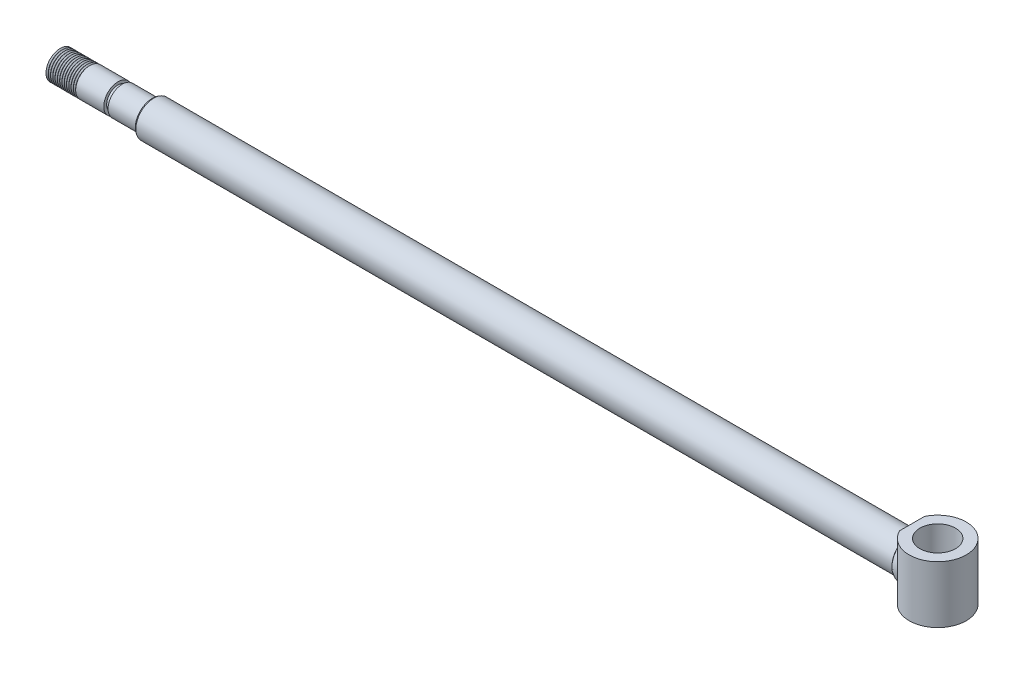
SolidWorks part; units mm, degrees
ref_plane "Front Plane" through (0, 0, 0) normal (0, 0, 1) x (1, 0, 0)
ref_plane "Top Plane" through (0, 0, 0) normal (0, 1, 0) x (1, 0, 0)
ref_plane "Right Plane" through (0, 0, 0) normal (1, 0, 0) x (0, 0, -1)
sketch "Sketch1" plane through (0, 0, 0) normal (0, 0, 1) x (1, 0, 0)
  line L0 (0, 0) -> (635, 0) construction
  line L1 (0, 0) -> (0, 10)
  line L2 (0, 0) -> (597, 0)
  line L3 (64.5, 10) -> (64.5, 12.5)
  line L4 (64.5, 12.5) -> (597, 12.5)
  line L5 (597, 12.5) -> (597, 0)
  line L6 (19.5, 10) -> (19.5, 0) construction
  line L7 (64.5, 10) -> (64.5, 0) construction
  line L8 (19.5, 5) -> (64.5, 5) construction
  line L9 (40.5, 10) -> (40.5, 8)
  line L10 (40.5, 8) -> (43.5, 8)
  line L11 (43.5, 8) -> (43.5, 10)
  line L12 (42, 5) -> (42, 10) construction
  line L13 (43.5, 10) -> (64.5, 10)
  line L14 (0, 10) -> (0.8, 9.2)
  line L15 (0.8, 9.2) -> (1.6, 10)
  line L16 (0.8, 9.2) -> (0.8, 10) construction
  line L17 (1.6, 10) -> (2.4, 9.2)
  line L18 (2.4, 9.2) -> (3.2, 10)
  line L19 (3.2, 10) -> (4, 9.2)
  line L20 (4, 9.2) -> (4.8, 10)
  line L21 (4.8, 10) -> (5.6, 9.2)
  line L22 (5.6, 9.2) -> (6.4, 10)
  line L23 (6.4, 10) -> (7.2, 9.2)
  line L24 (7.2, 9.2) -> (8, 10)
  line L25 (8, 10) -> (8.8, 9.2)
  line L26 (8.8, 9.2) -> (9.6, 10)
  line L27 (9.6, 10) -> (10.4, 9.2)
  line L28 (10.4, 9.2) -> (11.2, 10)
  line L29 (11.2, 10) -> (12, 9.2)
  line L30 (12, 9.2) -> (12.8, 10)
  line L31 (12.8, 10) -> (13.6, 9.2)
  line L32 (13.6, 9.2) -> (14.4, 10)
  line L33 (14.4, 10) -> (15.2, 9.2)
  line L34 (15.2, 9.2) -> (16, 10)
  line L35 (16, 10) -> (16.8, 9.2)
  line L36 (16.8, 9.2) -> (17.6, 10)
  line L37 (17.6, 10) -> (18.4, 9.2)
  line L38 (18.4, 9.2) -> (19.2, 10)
  line L39 (19.2, 10) -> (20, 9.2)
  line L40 (20, 9.2) -> (20.8, 10)
  line L41 (20.8, 10) -> (40.5, 10)
  dimension "D1" = 635
  dimension "D2" = 25
  dimension "D3" = 38
  dimension "D4" = 64.5
  dimension "D6" = 45
  dimension "D7" = 1.5
  dimension "D8" = 1.5
  dimension "D11" = 1.6
  dimension "D12" = 13
revolve "Revolve1" add sketch "Sketch1" angle 360 about L2
chamfer "Chamfer1" distance 1 angle 30 1 edges at (64.5, 0, 12.5) first distance on face at (64.5, 0, 12.5)
sketch "Sketch2" plane through (0, 0, 0) normal (0, 1, 0) x (1, 0, 0)
  line L0 (597, -12.5) -> (597, 12.5) construction
  line L1 (597, -12.5) -> (597, 12.5) construction
  line L2 (597, 0) -> (635, 0) construction
  line L3 (635, 0) -> (597, 0) construction
  line L4 (597, 0) -> (597, -8.7178)
  line L5 (597, 0) -> (597, 8.7178)
  arc A0 (597, -8.7178) -> (597, 8.7178) centre (615, 0) ccw
  circle A1 centre (615, 0) radius 12.5
  dimension "D2" = 40
  dimension "D3" = 38
  dimension "D5" = 25
  dimension "D1" = 38
  dimension "D4" = 0
extrude "Boss-Extrude1" add sketch "Sketch2" against normal blind 20 and the other way blind 20
sketch "Sketch3" plane through (0, 0, 0) normal (0, 0, 1) x (1, 0, 0)
  line L2 (597, 12.5) -> (65.5, 12.5) construction
  line L3 (597, 12.5) -> (595.5003, 12.5)
  line L4 (597, 12.5) -> (602.2973, 12.5)
  line L5 (602.2973, 12.5) -> (602.2973, 14.3636)
  spline S0 degree 2 poles (602.2973, 14.3636) (597.1908, 15.1081) (595.5003, 12.5) knots 0 0 0 0.822038 0.822038 0.822038
sketch "Sketch4" plane through (597, 0, 0) normal (-1, 0, 0) x (0, 0, 1)
  circle A8 centre (0, 0) radius 12.5
sketch "Sketch5" plane through (597, 0, 0) normal (1, 0, 0) x (0, 0, -1)
  line L1 (-8.7178, -8.9582) -> (-8.7178, 8.9582)
  line L2 (-8.7178, -8.9582) -> (-8.7178, 8.9582)
  arc A1 (-8.7178, 8.9582) -> (-8.7178, -8.9582) centre (0, 0) ccw
  arc A2 (-8.7178, 8.9582) -> (-8.7178, -8.9582) centre (0, 0) ccw
  dimension "D1" = 0
extrude "Boss-Extrude2" add sketch "Sketch5" along normal up to surface up to face at (606.5, 0, 0)
sketch "Sketch6" plane through (597, 0, 0) normal (1, 0, 0) x (0, 0, -1)
  line L1 (8.7178, 8.9582) -> (8.7178, -8.9582)
  line L2 (8.7178, 8.9582) -> (8.7178, -8.9582)
  arc A1 (8.7178, -8.9582) -> (8.7178, 8.9582) centre (0, 0) ccw
  arc A2 (8.7178, -8.9582) -> (8.7178, 8.9582) centre (0, 0) ccw
  dimension "D1" = 0
extrude "Boss-Extrude3" add sketch "Sketch6" along normal up to surface up to face at (606.7868, -0.2135, 0.4581)
sweep "Sweep3" add profiles "Sketch3" path "Sketch4"
